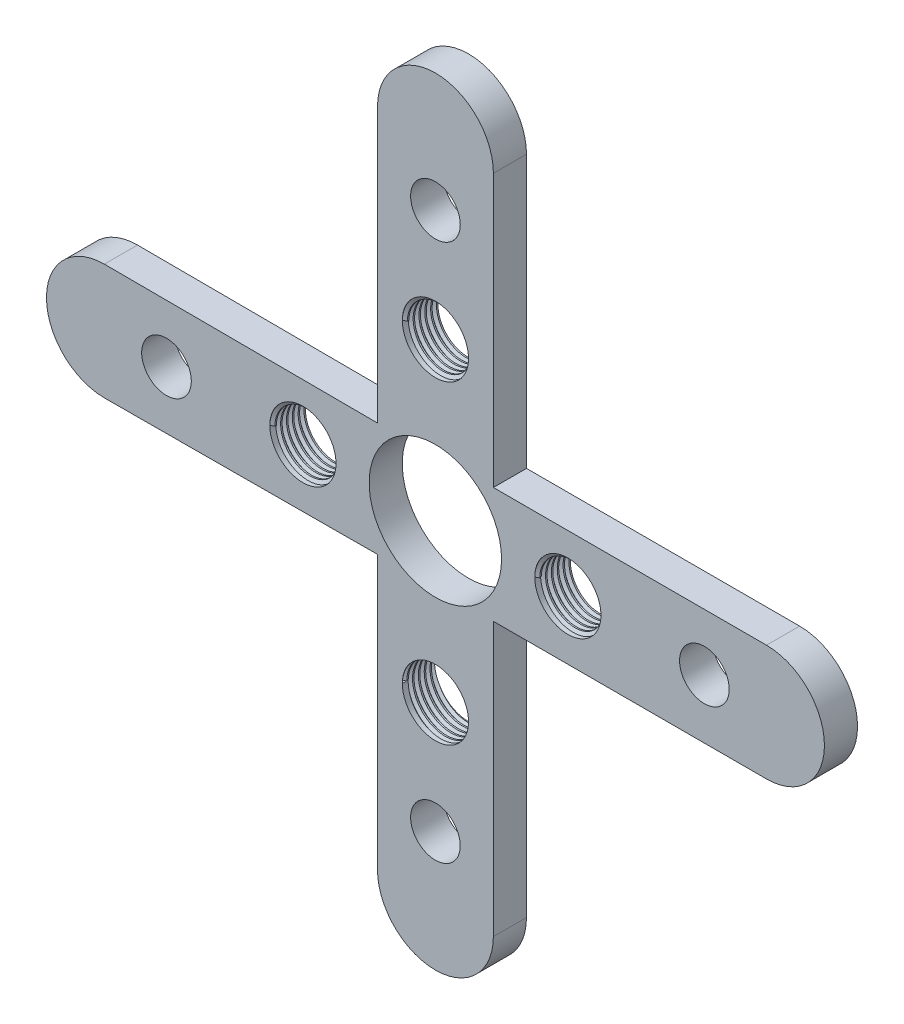
SolidWorks part; units mm, degrees
ref_plane "Front Plane" through (0, 0, 0) normal (0, 0, 1) x (1, 0, 0)
ref_plane "Top Plane" through (0, 0, 0) normal (0, 1, 0) x (1, 0, 0)
ref_plane "Right Plane" through (0, 0, 0) normal (1, 0, 0) x (0, 0, -1)
sketch "Sketch1" plane through (0, 0, 0) normal (0, 0, 1) x (1, 0, 0)
  line L14 (-21.4121, 11.1573) -> (-4.9138, 11.1573)
  line L15 (-4.9138, 4.1573) -> (-21.4138, 4.1573)
  line L18 (-28.4121, 27.5938) -> (-28.4121, 11.0303)
  line L20 (-21.4121, 27.5938) -> (-21.4121, 11.1573)
  line L21 (-28.4138, -12.3427) -> (-28.4138, 4.1573)
  line L25 (-21.4138, -12.3427) -> (-21.4138, 4.1573)
  line L26 (-44.9114, 4.0938) -> (-28.4138, 4.1573)
  line L27 (-44.9114, 11.0938) -> (-28.4121, 11.0303)
  circle A4 centre (-24.9186, 7.6573) radius 4
  circle A5 centre (-24.9138, 23.9073) radius 1.5
  circle A6 centre (-24.9138, -8.5927) radius 1.5
  circle A7 centre (-24.9138, -1.8451) radius 1.5
  circle A8 centre (-24.9138, 17.1536) radius 1.5
  circle A9 centre (-24.9138, 17.1536) radius 2
  circle A10 centre (-24.9138, -1.8451) radius 2
  circle A11 centre (-16.9141, 7.7208) radius 1.5
  circle A12 centre (-16.9141, 7.7208) radius 2
  circle A13 centre (-32.9186, 7.6573) radius 1.5
  circle A14 centre (-32.9186, 7.6573) radius 2
  circle A15 centre (-41.1614, 7.5938) radius 1.5
  circle A16 centre (-8.6655, 7.7208) radius 1.5
  arc A17 (-28.4121, 27.5938) -> (-21.4121, 27.5938) centre (-24.9121, 27.5938) cw
  arc A18 (-4.9138, 11.1573) -> (-4.9138, 4.1573) centre (-4.9138, 7.6573) cw
  arc A19 (-21.4138, -12.3427) -> (-28.4138, -12.3427) centre (-24.9138, -12.3427) cw
  arc A20 (-44.9114, 4.0938) -> (-44.9114, 11.0938) centre (-44.9114, 7.5938) cw
  dimension "D1" = 32.5
  dimension "D5" = 16.5
  dimension "D2" = 18.9986
  dimension "D3" = 16.0046
  dimension "D4" = 32.4958
  dimension "D6" = 16.5
  dimension "D7" = 16.5
extrude "Boss-Extrude2" add sketch "Sketch1" along normal blind 2 contours A20 L26 L21 A19 L25 L15 A18 L14 L20 A17 L18 L27 A16 A15 A14 A12 A10 A9 A6 A5 A4 region at (-13.163, 10.4931, 0)
thread "Thread1" pitch 0.3528 method extrude profile "Thread Profile1" start angle 0, offset 0, length 2, pitch 0.3528, diameter 4
ref_plane "Plane1" through (-26.9138, 17.1536, 2) normal (0, -1, 0) x (-1, 0, 0)
sketch "Thread Profile1" plane through (-26.9138, 17.1536, 2) normal (0, -1, 0) x (-1, 0, 0)
  line L0 (0, 0) -> (0, 0.3528) construction
  line L11 (0, 0) -> (0, 0.3087)
  line L12 (0, 0.3087) -> (-0.1909, 0.1984)
  line L13 (-0.1909, 0.1984) -> (-0.1909, 0.1102)
  line L15 (-0.1909, 0.1102) -> (0, 0)
  line L17 (-0.1909, 0.1543) -> (0, 0.1543) construction
  point P2 (0, 0)
  dimension "Pitch" = 0.3528
  dimension "Profile_Angle" = 60
  dimension "Profile_Land" = 0.0882
  dimension "Profile_Height" = 0.1909
thread "Thread2" pitch 0.3528 method extrude profile "Thread Profile2" start angle 0, offset 0, length 2, pitch 0.3528, diameter 4
ref_plane "Plane2" through (-34.9186, 7.6573, 2) normal (0, -1, 0) x (-1, 0, 0)
sketch "Thread Profile2" plane through (-34.9186, 7.6573, 2) normal (0, -1, 0) x (-1, 0, 0)
  line L0 (0, 0) -> (0, 0.3528) construction
  line L11 (0, 0) -> (0, 0.3087)
  line L12 (0, 0.3087) -> (-0.1909, 0.1984)
  line L13 (-0.1909, 0.1984) -> (-0.1909, 0.1102)
  line L15 (-0.1909, 0.1102) -> (0, 0)
  line L17 (-0.1909, 0.1543) -> (0, 0.1543) construction
  point P2 (0, 0)
  dimension "Pitch" = 0.3528
  dimension "Profile_Angle" = 60
  dimension "Profile_Land" = 0.0882
  dimension "Profile_Height" = 0.1909
thread "Thread3" pitch 0.3528 method extrude profile "Thread Profile3" start angle 0, offset 0, length 2, pitch 0.3528, diameter 4
ref_plane "Plane3" through (-18.9141, 7.7208, 2) normal (0, -1, 0) x (-1, 0, 0)
sketch "Thread Profile3" plane through (-18.9141, 7.7208, 2) normal (0, -1, 0) x (-1, 0, 0)
  line L0 (0, 0) -> (0, 0.3528) construction
  line L11 (0, 0) -> (0, 0.3087)
  line L12 (0, 0.3087) -> (-0.1909, 0.1984)
  line L13 (-0.1909, 0.1984) -> (-0.1909, 0.1102)
  line L15 (-0.1909, 0.1102) -> (0, 0)
  line L17 (-0.1909, 0.1543) -> (0, 0.1543) construction
  point P2 (0, 0)
  dimension "Pitch" = 0.3528
  dimension "Profile_Angle" = 60
  dimension "Profile_Land" = 0.0882
  dimension "Profile_Height" = 0.1909
thread "Thread4" pitch 0.3528 method cut profile "Thread Profile4" start angle 0, offset 0, length 2, pitch 0.3528, diameter 4
ref_plane "Plane4" through (-26.9138, -1.8451, 2) normal (0, -1, 0) x (-1, 0, 0)
sketch "Thread Profile4" plane through (-26.9138, -1.8451, 2) normal (0, -1, 0) x (-1, 0, 0)
  line L0 (0, 0) -> (0, 0.3528) construction
  line L1 (0, 0) -> (0.1909, 0.1102)
  line L2 (0.1909, 0.1102) -> (0.1909, 0.1543)
  line L3 (0.1909, 0.1543) -> (0, 0.2646)
  line L4 (0.1909, 0.1323) -> (0, 0.1323) construction
  line L11 (0, 0) -> (0, 0.2646)
  point P2 (0, 0)
  dimension "Pitch" = 0.3528
  dimension "Profile_Angle" = 60
  dimension "Profile_Land" = 0.0441
  dimension "Profile_Height" = 0.1909
